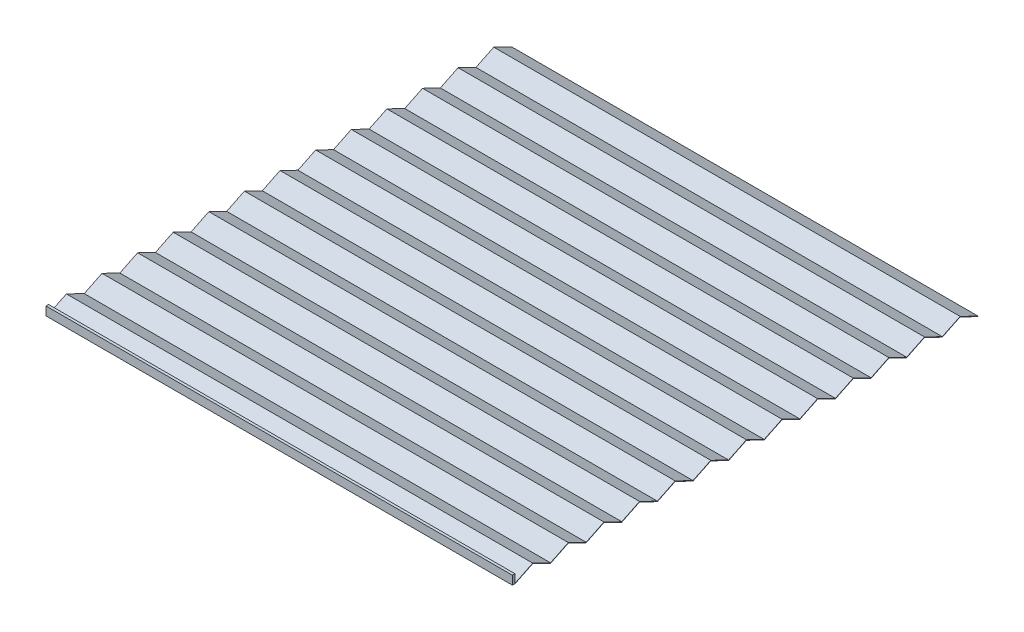
SolidWorks part; units mm, degrees
ref_plane "Front Plane" through (0, 0, 0) normal (0, 0, 1) x (1, 0, 0)
ref_plane "Top Plane" through (0, 0, 0) normal (0, 1, 0) x (1, 0, 0)
ref_plane "Right Plane" through (0, 0, 0) normal (1, 0, 0) x (0, 0, -1)
sketch "Sketch2" plane through (0, 0, 0) normal (0, 0, 1) x (1, 0, 0)
  line L1 (-270, 10) -> (270, 10)
  line L2 (-270, 10) -> (-270, 0)
  line L3 (-270, 0) -> (270, 0)
  line L4 (270, 10) -> (270, 0)
  point P4 (0, 0)
  dimension "D1" = 10
  dimension "D2" = 540
extrude "Boss-Extrude1" add sketch "Sketch2" along normal blind 3
sketch "Sketch3" plane through (270, 0, 0) normal (1, 0, 0) x (0, 0, -1)
  line L0 (0, 10) -> (536.1116, 10) construction
  line L1 (0, 0) -> (536.1116, 0) construction
  line L2 (536.1116, 10) -> (536.1116, 0) construction
  line L3 (0, 0) -> (20.6197, 10)
  line L4 (20.6197, 10) -> (41.2394, 0)
  line L5 (41.2394, 0) -> (61.859, 10)
  line L6 (61.859, 10) -> (82.4787, 0)
  line L7 (82.4787, 0) -> (103.0984, 10)
  line L8 (103.0984, 10) -> (123.7181, 0)
  line L9 (123.7181, 0) -> (144.3377, 10)
  line L10 (144.3377, 10) -> (164.9574, 0)
  line L11 (164.9574, 0) -> (185.5771, 10)
  line L12 (185.5771, 10) -> (206.1968, 0)
  line L13 (206.1968, 0) -> (226.8164, 10)
  line L14 (226.8164, 10) -> (247.4361, 0)
  line L15 (247.4361, 0) -> (268.0558, 10)
  line L16 (268.0558, 10) -> (288.6755, 0)
  line L17 (288.6755, 0) -> (309.2952, 10)
  line L18 (309.2952, 10) -> (329.9148, 0)
  line L20 (329.9148, 0) -> (350.5345, 10)
  line L21 (350.5345, 10) -> (371.1542, 0)
  line L22 (371.1542, 0) -> (391.7739, 10)
  line L23 (391.7739, 10) -> (412.3935, 0)
  line L24 (412.3935, 0) -> (433.0132, 10)
  line L25 (433.0132, 10) -> (453.6329, 0)
  line L26 (453.6329, 0) -> (474.2526, 10)
  line L27 (474.2526, 10) -> (494.8722, 0)
  line L28 (494.8722, 0) -> (515.4919, 10)
  line L29 (515.4919, 10) -> (536.1116, 0)
  line L30 (536.1116, 10) -> (536.1116, 0) construction
extrude "Extrude-Thin1" add sketch "Sketch3" against normal through all thin thin type mid plane wall 0.5
